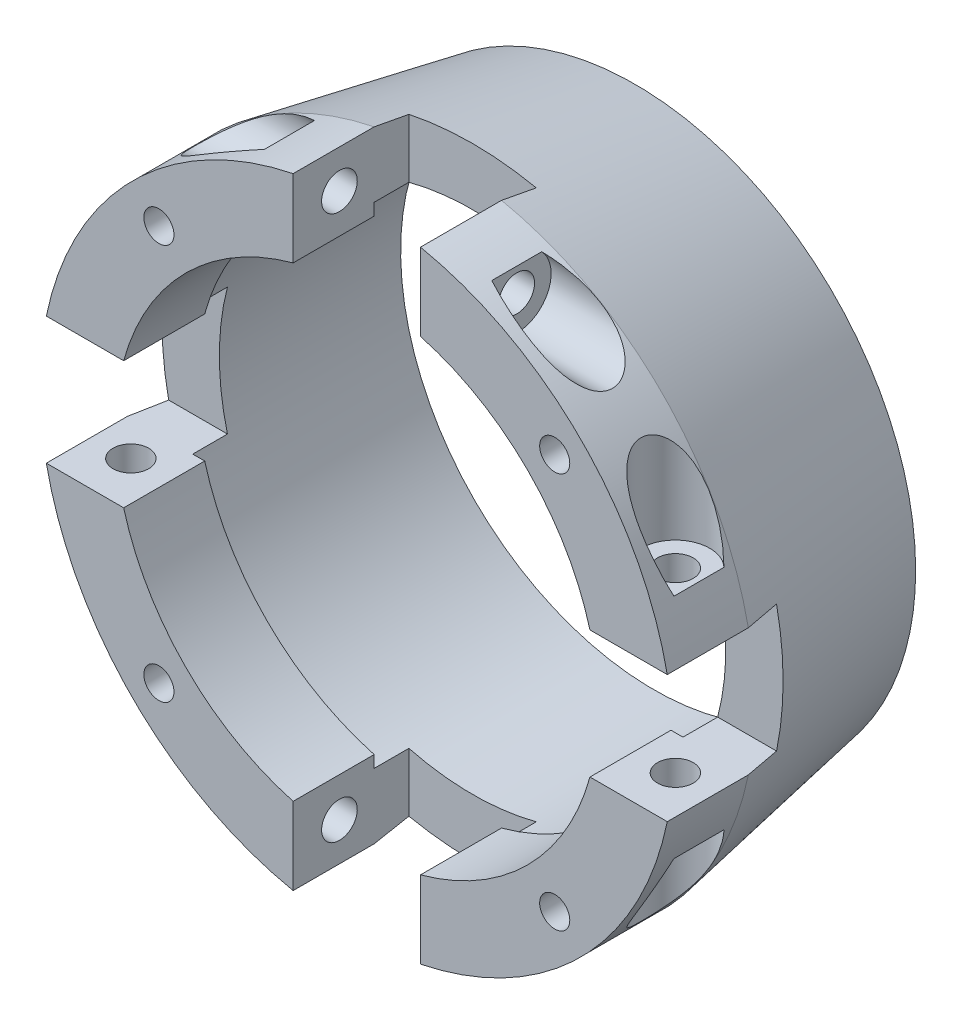
SolidWorks part; units mm, degrees
ref_plane "Front Plane" through (0, 0, 0) normal (1, 0, 0) x (0, 1, 0)
ref_plane "Top Plane" through (0, 0, 0) normal (0, 0, 1) x (0, 1, 0)
ref_plane "Right Plane" through (0, 0, 0) normal (0, 1, 0) x (-1, 0, 0)
sketch "Sketch1" plane through (0, 0, 0) normal (1, 0, 0) x (0, 1, 0)
  line L0 (0, 0) -> (27.7812, 0) construction
  line L1 (0, 0) -> (0, 33.02) construction
  line L2 (27.7812, 0) -> (27.7812, 24.13)
  line L3 (27.7812, 24.13) -> (26.5113, 24.13)
  line L4 (26.5113, 24.13) -> (26.5113, 33.02)
  line L8 (0, 33.02) -> (26.5113, 33.02) construction
  line L11 (27.7812, 0) -> (30.3213, 0)
  line L13 (34.7662, 33.02) -> (26.5113, 33.02)
  line L15 (34.7662, 33.02) -> (34.7662, 24.13)
  line L16 (34.7662, 24.13) -> (30.3213, 0)
  line L17 (27.7812, 24.13) -> (34.7662, 24.13) construction
  dimension "D1" = 27.7812
  dimension "D2" = 24.13
  dimension "D3" = 8.89
  dimension "D4" = 1.27
  dimension "D5" = 8.255
  dimension "D6" = 2.54
  dimension "D7" = 34.7662
  dimension "D8" = 33.02
revolve "base_ring" add sketch "Sketch1" angle 360 about L1
sketch "Sketch5" plane through (0, 0, 33.02) normal (0, 0, 1) x (1, 0, 0)
  line L0 (0, 0) -> (0, 25.5745) construction
  line L1 (-6.985, 38.2745) -> (6.985, 38.2745)
  line L2 (-6.985, 38.2745) -> (-6.985, 25.5745)
  line L3 (-6.985, 25.5745) -> (6.985, 25.5745)
  line L4 (6.985, 38.2745) -> (6.985, 25.5745)
  circle A0 centre (0, 0) radius 26.5113 construction
  dimension "D1" = 13.97
  dimension "D2" = 12.7
extrude "pulley_recess" cut sketch "Sketch5" against normal blind 12.7 and the other way through all
ref_plane "Plane1" through (34.7662, 0, 0) normal (1, 0, 0) x (0, 0, -1)
sketch "Sketch7" plane through (34.7662, 0, 0) normal (1, 0, 0) x (0, 0, -1)
  line L6 (-27.94, 29.8663) -> (-27.94, 34.0573) construction
  line L7 (-24.13, 34.0573) -> (-33.02, 34.0573) construction
  line L9 (-24.13, 34.0573) -> (-24.13, -34.7662) construction
  point P0 (-27.94, 29.8663)
  dimension "D1" = 3.81
  dimension "D2" = 4.191
hole_wizard "pulley_bolt_hole" positions "Sketch7" profile "Sketch8" counterbore size "#5" standard "ANSI Inch"
sketch "Sketch8" plane through (34.7662, 29.8663, 27.94) normal (0, 1, 0) x (0, 0, -1)
  line L0 (0, 0) -> (0, 39.2752)
  line L1 (0, 39.2752) -> (1.9558, 38.1)
  line L2 (1.9558, 38.1) -> (1.9558, 22.3012)
  line L3 (1.9558, 22.3012) -> (3.7706, 22.3012)
  line L4 (3.7706, 22.3012) -> (3.7706, 0)
  line L5 (3.7706, 0) -> (0, 0)
  line L10 (0, 39.2752) -> (-1.9558, 38.1) construction
  line L11 (0, -6.35) -> (0, 107.95) construction
  dimension "Hole Dia." = 3.9116
  dimension "Hole Depth" = 38.1
  dimension "C'Bore Dia." = 7.5413
  dimension "C'Bore Depth" = 22.3012
  dimension "Drill Angle" = 118
mirror "bolthole_mirror" about plane through (0, 0, 0) normal (1, 0, 0) of "pulley_bolt_hole"
sketch "Sketch11" plane through (0, 0, 33.02) normal (0, 0, 1) x (1, 0, 0)
  line L0 (0, 0) -> (24.5835, 24.5835) construction
  line L3 (0, 0) -> (0, 34.0644) construction
  circle A0 centre (21.7098, 21.7098) radius 1.651
  arc A3 (6.985, 33.3406) -> (-6.985, 33.3406) centre (0, 0) ccw construction
  arc A4 (-6.985, 34.0573) -> (6.985, 34.0573) centre (0, 0) ccw construction
  dimension "D1" = 3.302
  dimension "D2" = 4.064
  dimension "D3" = 45
extrude "nosecone_pin_hole" cut sketch "Sketch11" against normal blind 10.16
pattern_circular "CirPattern1" count 4 over 360 about axis through (0, 0, 0) along (0, 0, -1) of "pulley_recess", "pulley_bolt_hole", "bolthole_mirror", "nosecone_pin_hole"
chamfer "Chamfer1" distance 2.54 angle 45 1 edges at (-30.3213, 0, 0) first distance on face at (-30.3213, 0, 0)
